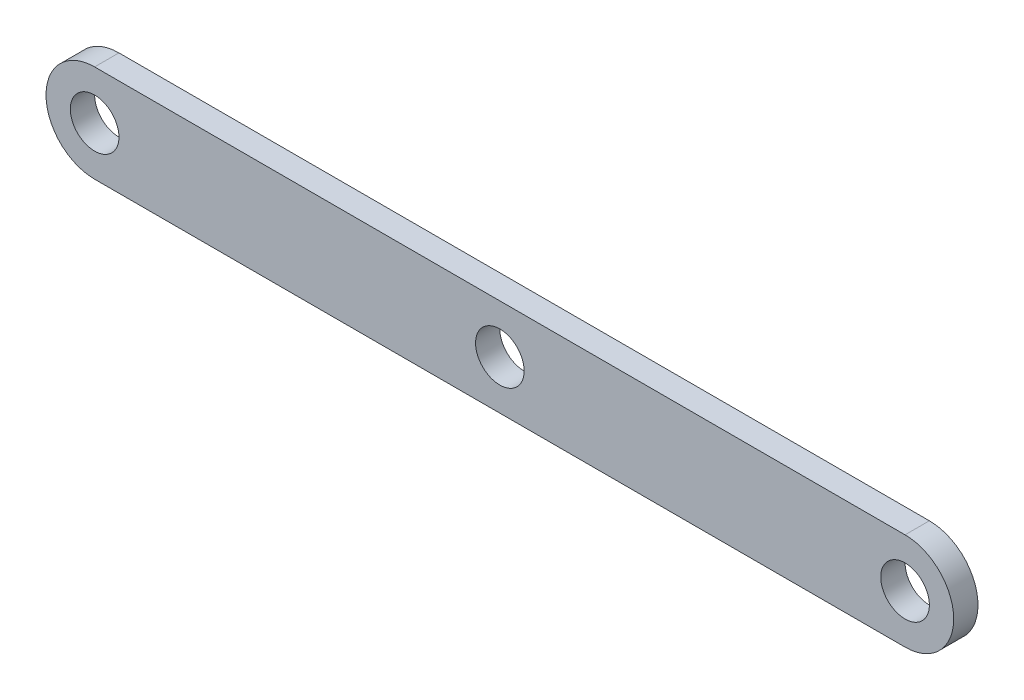
SolidWorks part; units mm, degrees
ref_plane "Front Plane" through (0, 0, 0) normal (0, 0, 1) x (1, 0, 0)
ref_plane "Top Plane" through (0, 0, 0) normal (0, 1, 0) x (1, 0, 0)
ref_plane "Right Plane" through (0, 0, 0) normal (1, 0, 0) x (0, 0, -1)
sketch "Sketch1" plane through (0, 0, 0) normal (0, 0, 1) x (1, 0, 0)
  line L0 (-50, 0) -> (50, 0) construction
  line L1 (-50, 6) -> (50, 6)
  line L2 (-50, -6) -> (50, -6)
  arc A0 (-50, 6) -> (-50, -6) centre (-50, 0) ccw
  arc A1 (50, -6) -> (50, 6) centre (50, 0) ccw
  circle A2 centre (-50, 0) radius 3
  circle A3 centre (50, 0) radius 3
  circle A4 centre (0, 0) radius 3
  point P3 (0, 0)
  dimension "D1" = 6
  dimension "D2" = 6
  dimension "D3" = 100
extrude "Boss-Extrude1" add sketch "Sketch1" along normal blind 3
